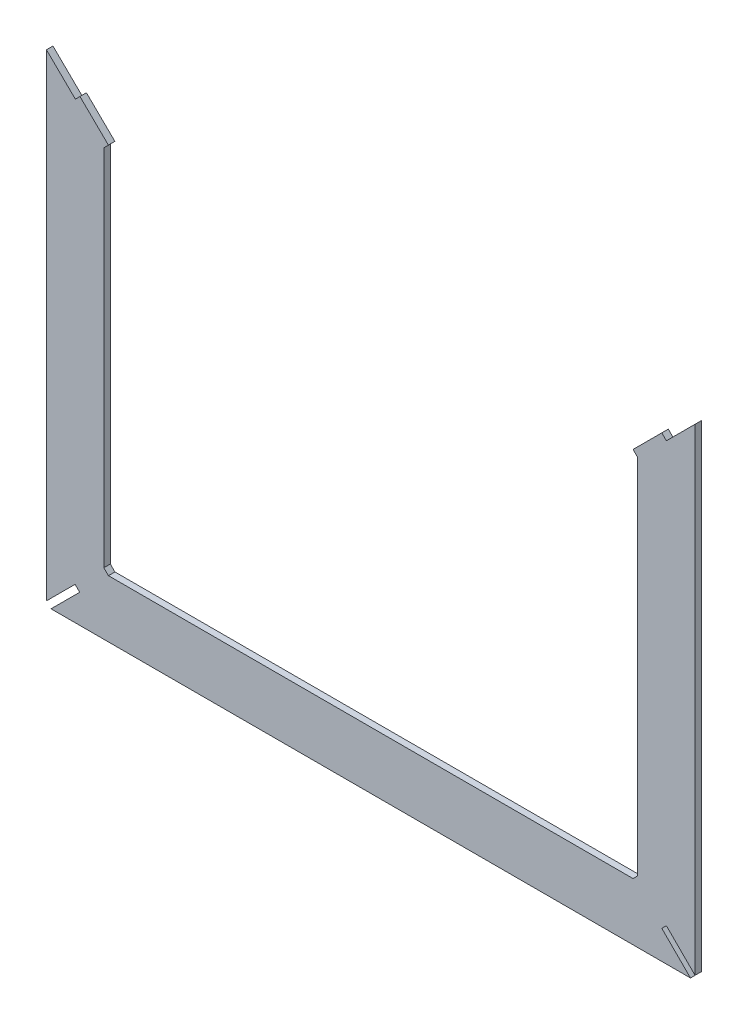
SolidWorks part; units mm, degrees
ref_plane "Plan de face" through (0, 0, 0) normal (0, 0, 1) x (1, 0, 0)
ref_plane "Plan de dessus" through (0, 0, 0) normal (0, 1, 0) x (1, 0, 0)
ref_plane "Plan de droite" through (0, 0, 0) normal (1, 0, 0) x (0, 0, -1)
sketch "Esquisse1" plane through (0, 0, 0) normal (0, 0, 1) x (1, 0, 0)
  line L0 (-72.3879, -137.1329) -> (-69.5594, -134.3045)
  line L1 (-69.5594, 94.8955) -> (-72.3879, 92.0671)
  line L2 (-434.1594, 127.4671) -> (-434.1594, -172.5329) construction
  line L3 (-434.1594, -172.5329) -> (-34.1594, -172.5329) construction
  line L4 (-34.1594, 127.4671) -> (-34.1594, -172.5329) construction
  line L5 (-434.1594, 124.6387) -> (-434.1594, -169.7045)
  line L6 (-431.331, -172.5329) -> (-36.9879, -172.5329)
  line L7 (-34.1594, -169.7045) -> (-34.1594, 124.6387)
  line L8 (-34.1594, 124.6387) -> (-51.8371, 106.961)
  line L9 (-51.8371, 106.961) -> (-54.6655, 109.7894)
  line L10 (-395.931, -137.1329) -> (-72.3879, -137.1329)
  line L11 (-34.1594, -169.7045) -> (-51.8371, -152.0268)
  line L12 (-51.8371, -152.0268) -> (-54.6655, -154.8552)
  line L13 (-54.6655, -154.8552) -> (-36.9879, -172.5329)
  line L14 (-431.331, -172.5329) -> (-413.6533, -154.8552)
  line L15 (-413.6533, -154.8552) -> (-416.4818, -152.0268)
  line L16 (-416.4818, -152.0268) -> (-434.1594, -169.7045)
  line L17 (-398.7594, -134.3045) -> (-395.931, -137.1329)
  line L18 (-413.5004, 110.003) -> (-416.2993, 107.1454)
  line L19 (-416.2993, 107.1454) -> (-434.1594, 124.6387)
  line L20 (-395.9605, 92.8234) -> (-398.7594, 89.9658)
  line L21 (-69.5594, -134.3045) -> (-69.5594, -137.1329) construction
  line L22 (-69.5594, -137.1329) -> (-72.3879, -137.1329) construction
  line L23 (-69.5594, 94.8955) -> (-54.6655, 109.7894)
  line L24 (-395.9605, 92.8234) -> (-413.5004, 110.003)
  line L25 (-398.7594, -134.3045) -> (-398.7594, -137.1329) construction
  line L26 (-398.7594, -137.1329) -> (-395.931, -137.1329) construction
  line L27 (-72.3879, 92.0671) -> (-69.5594, 89.2387)
  line L28 (-69.5594, 89.2387) -> (-69.5594, -134.3045)
  line L29 (-398.7594, 89.9658) -> (-398.7594, -134.3045)
  dimension "D1" = 300
  dimension "D2" = 400
  dimension "D3" = 4
  dimension "D4" = 25
  dimension "D5" = 45
  dimension "D6" = 45
  dimension "D7" = 45
  dimension "D8" = 45
  dimension "D9" = 35.4
  dimension "D10" = 4
  dimension "D11" = 35.4
  dimension "D12" = 4
  dimension "D13" = 35.4
extrude "Boss.-Extru.1" add sketch "Esquisse1" along normal blind 4
